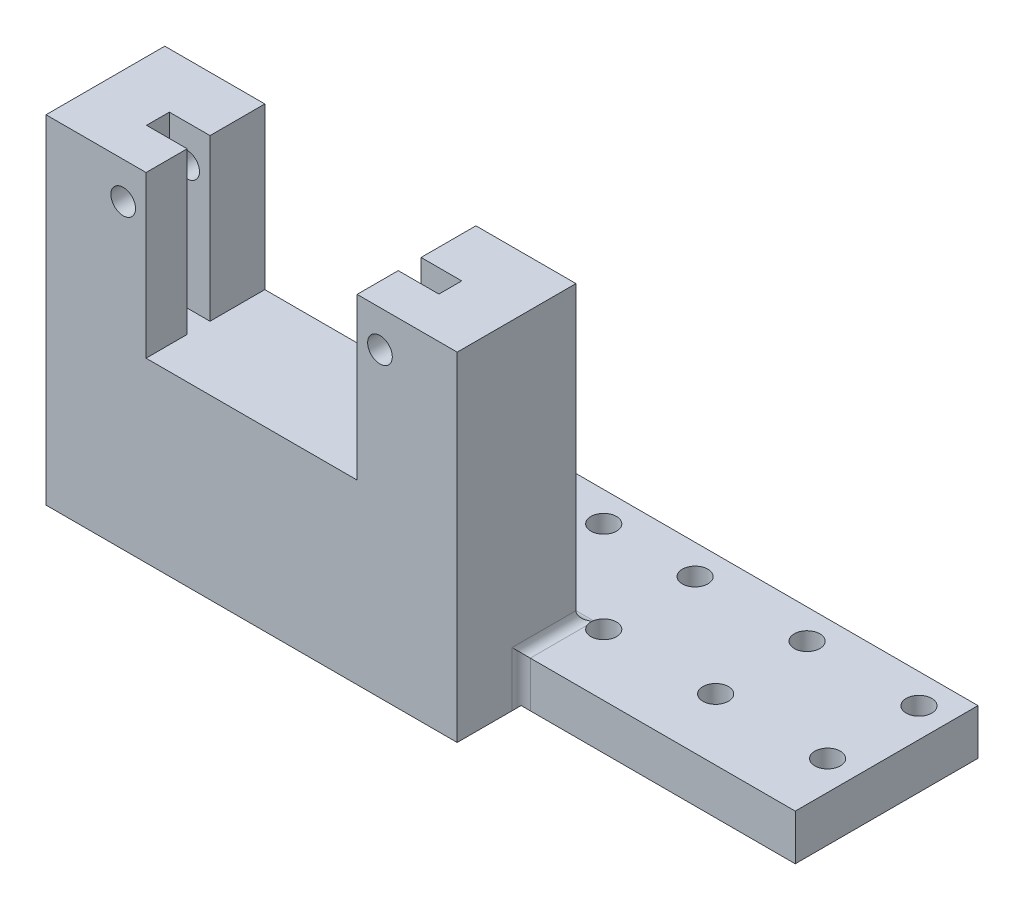
SolidWorks part; units mm, degrees
material "ABS"
ref_plane "Front Plane" through (0, 0, 0) normal (0, 0, 1) x (1, 0, 0)
ref_plane "Top Plane" through (0, 0, 0) normal (0, 1, 0) x (1, 0, 0)
ref_plane "Right Plane" through (0, 0, 0) normal (1, 0, 0) x (0, 0, -1)
sketch "Sketch1" plane through (0, 0, 0) normal (0, 1, 0) x (1, 0, 0)
  line L1 (0, 0) -> (45, 0)
  line L2 (0, 0) -> (0, 6)
  line L3 (0, 6) -> (45, 6)
  line L4 (45, 0) -> (45, 6)
  dimension "D1" = 45
  dimension "D2" = 6
extrude "Boss-Extrude1" add sketch "Sketch1" along normal blind 32
sketch "Sketch2" plane through (0, 0, 0) normal (0, 0, 1) x (1, 0, 0)
  line L0 (0, 32) -> (45, 32) construction
  line L2 (10.95, 32) -> (10.95, 14.4)
  line L3 (10.95, 14.4) -> (34.05, 14.4)
  line L4 (34.05, 32) -> (34.05, 14.4)
  line L5 (10.95, 32) -> (34.05, 32)
  line L6 (22.5, 14.4) -> (22.5, 0) construction
  line L7 (0, 0) -> (45, 0) construction
  dimension "D1" = 23.1
  dimension "D3" = 14.4
extrude "Cut-Extrude1" cut sketch "Sketch2" against normal through all
sketch "Sketch3" plane through (0, 0, 0) normal (0, -1, 0) x (1, 0, 0)
  line L0 (45, 0) -> (45, -6) construction
  line L1 (0, 0) -> (45, 0)
  line L2 (0, 0) -> (0, -20)
  line L3 (0, -20) -> (45, -20)
  line L4 (45, 0) -> (45, -20)
  dimension "D1" = 20
extrude "Boss-Extrude2" add sketch "Sketch3" along normal blind 6
sketch "Sketch4" plane through (45, 0, 0) normal (1, 0, 0) x (0, 0, -1)
  line L1 (20, 0) -> (0, 0)
  line L2 (20, 0) -> (20, -6)
  line L3 (20, -6) -> (0, -6)
  line L4 (0, 0) -> (0, -6)
extrude "Boss-Extrude3" add sketch "Sketch4" along normal blind 30
sketch "Sketch5" plane through (0, -6, 0) normal (0, -1, 0) x (1, 0, 0)
  line L0 (47.2888, -6.75) -> (59.5388, -6.75) construction
  line L1 (37.2888, -16.75) -> (47.2888, -16.75) construction
  line L2 (47.2888, -16.75) -> (59.5388, -16.75) construction
  line L3 (59.5388, -16.75) -> (71.7888, -16.75) construction
  line L4 (71.7888, -16.75) -> (71.7888, -6.75) construction
  line L5 (59.5388, -6.75) -> (59.5388, -16.75) construction
  line L6 (47.2888, -6.75) -> (47.2888, -16.75) construction
  line L7 (0, -20) -> (75, -20) construction
  line L8 (75, 0) -> (75, -20) construction
  line L9 (59.5388, -6.75) -> (71.7888, -6.75) construction
  circle A1 centre (37.2888, -16.75) radius 1.4
  circle A5 centre (47.2888, -16.75) radius 1.4
  circle A7 centre (47.2888, -6.75) radius 1.4
  circle A9 centre (59.5388, -16.75) radius 1.4
  circle A11 centre (71.7888, -16.75) radius 1.4
  circle A13 centre (71.7888, -6.75) radius 1.4
  circle A14 centre (59.5388, -6.75) radius 1.4
  dimension "D1" = 10
  dimension "D2" = 12.25
  dimension "D6" = 2.8
  dimension "D7" = 3.2112
  dimension "D3" = 12.25
  dimension "D4" = 3.25
  dimension "D5" = 10
extrude "Cut-Extrude2" cut sketch "Sketch5" against normal through all
sketch "Sketch6" plane through (0, 0, 0) normal (0, 0, 1) x (1, 0, 0)
  line L0 (0, -6) -> (0, 32)
  line L1 (0, 32) -> (10.95, 32)
  line L2 (10.95, 32) -> (10.95, 14.4)
  line L3 (10.95, 14.4) -> (34.05, 14.4)
  line L4 (34.05, 14.4) -> (34.05, 32)
  line L5 (34.05, 32) -> (45, 32)
  line L6 (45, 32) -> (45, -6)
  line L7 (75, -6) -> (0, -6) construction
  line L8 (45, -6) -> (-0.8534, -6)
  line M1 (45, 32) -> (34.05, 32)
  line M2 (34.05, 32) -> (34.05, 14.4)
  line M3 (34.05, 14.4) -> (10.95, 14.4)
  line M4 (10.95, 14.4) -> (10.95, 32)
  line M5 (10.95, 32) -> (0, 32)
  line M6 (0, 32) -> (0, -6)
  line M7 (0, -6) -> (75, -6)
  line M10 (45, 0) -> (45, 32)
extrude "Boss-Extrude4" add sketch "Sketch6" along normal blind 7 contours L6 M10 M1 M2 M3 M4 M5 M6 M7 region at (22.5, 9.8185, 0)
sketch "Sketch7" plane through (0, 32, 0) normal (0, 1, 0) x (1, 0, 0)
  line L1 (6.5, 0) -> (38.5, 0)
  line L2 (6.5, 0) -> (6.5, -2.5)
  line L3 (6.5, -2.5) -> (38.5, -2.5)
  line L4 (38.5, 0) -> (38.5, -2.5)
  line L5 (22.5, 6) -> (22.5, 0) construction
  line L6 (10.95, 6) -> (34.05, 6) construction
  dimension "D1" = 2.5
  dimension "D2" = 32
extrude "Cut-Extrude3" cut sketch "Sketch7" against normal up to surface (17.6 mm away) up to face at (22.5, 14.4, 0.5)
sketch "Sketch8" plane through (0, 0, 7) normal (0, 0, 1) x (1, 0, 0)
  line L0 (10.95, 32) -> (0, 32) construction
  line L1 (10.95, 14.4) -> (10.95, 32) construction
  line L2 (34.05, 32) -> (34.05, 14.4) construction
  circle A0 centre (8.45, 28) radius 1.35
  circle A1 centre (36.55, 28) radius 1.35
  dimension "D1" = 2.7
  dimension "D3" = 2.5
  dimension "D2" = 4
  dimension "D4" = 2.5
extrude "Cut-Extrude4" cut sketch "Sketch8" against normal through all
chamfer "Chamfer1" distance 1 angle 45 6 edges at (0, -6, -6.5) (37.5, -6, -20) (75, -6, -10) (60, -6, 0) (45, -6, 3.5) (22.5, -6, 7)
fillet "Fillet1" radius 1 3 edges at (22.5, 0, -6) (45, 0, -3) (45, -2.5, 0)
